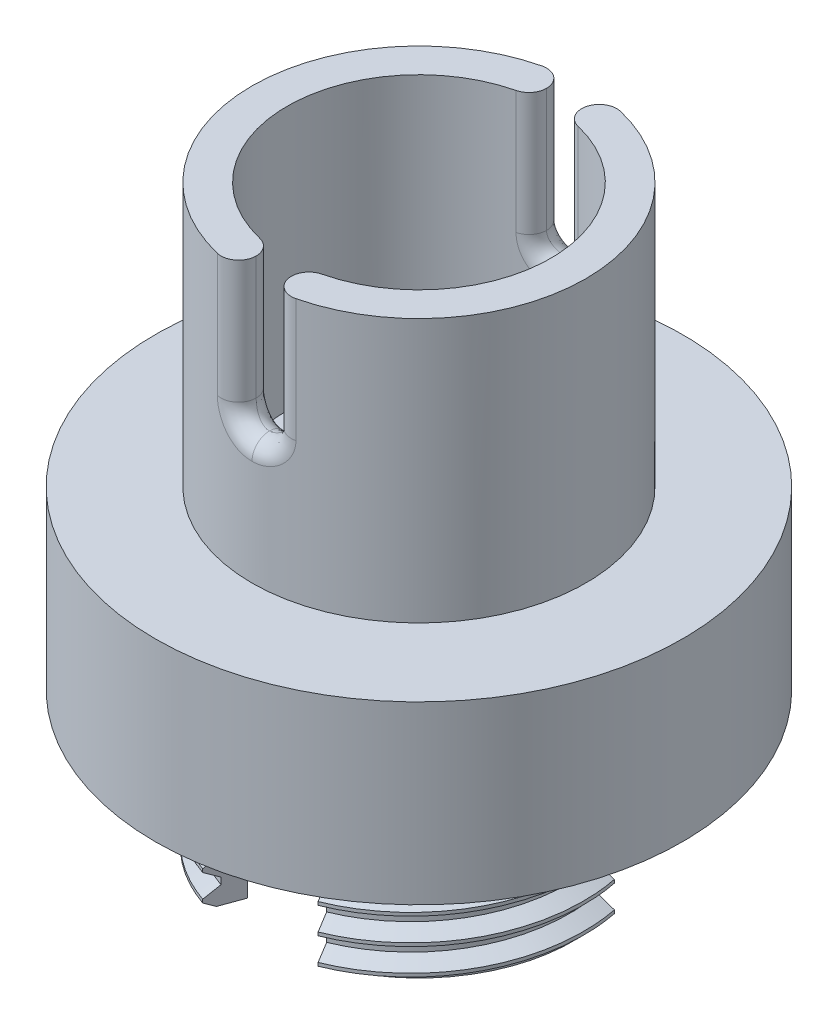
SolidWorks part; units mm, degrees
ref_plane "Front" through (0, 0, 0) normal (0, 0, 1) x (1, 0, 0)
ref_plane "Top" through (0, 0, 0) normal (0, 1, 0) x (1, 0, 0)
ref_plane "Right" through (0, 0, 0) normal (1, 0, 0) x (0, 0, -1)
sketch "Sketch1" plane through (0, 0, 0) normal (0, 1, 0) x (1, 0, 0)
  circle A0 centre (0, 0) radius 15
extrude "Boss-Extrude1" add sketch "Sketch1" along normal blind 10
sketch "Sketch2" plane through (0, 10, 0) normal (0, 1, 0) x (1, 0, 0)
  circle A0 centre (0, 0) radius 7.5
  circle A1 centre (0, 0) radius 9.5
extrude "Boss-Extrude2" add sketch "Sketch2" along normal blind 15
sketch "Sketch3" plane through (0, 0, 0) normal (0, -1, 0) x (1, 0, 0)
  circle A0 centre (0, 0) radius 7.6
  circle A1 centre (0, 0) radius 9.6
extrude "Boss-Extrude3" add sketch "Sketch3" along normal blind 8
sketch "Sketch4" plane through (0, 0, 0) normal (0, 0, 1) x (1, 0, 0)
  line L0 (0, 9.9863) -> (0, -13.3125) construction
  line L1 (0, 7.6) -> (0, -7.6)
  arc A1 (0, 7.6) -> (0, -7.6) centre (0, 0) cw
revolve "Cut-Revolve1" cut sketch "Sketch4" angle 360 about L0
sketch "Sketch5" plane through (0, -8, 0) normal (0, -1, 0) x (1, 0, 0)
  line L0 (0, 16.258) -> (0, 0) construction
  line L1 (-3.2834, 9.021) -> (-2.5994, 7.1417)
  line L2 (3.2834, 9.021) -> (2.5994, 7.1417)
  line L3 (9.4542, -1.667) -> (7.4845, -1.3197)
  line L4 (6.1708, -7.354) -> (4.8852, -5.8219)
  line L5 (-6.1708, -7.354) -> (-4.8852, -5.8219)
  line L6 (-9.4542, -1.667) -> (-7.4845, -1.3197)
  circle A0 centre (0, 0) radius 9.6 construction
  circle A1 centre (0, 0) radius 7.6 construction
  arc A2 (-3.2834, 9.021) -> (3.2834, 9.021) centre (0, 0) cw
  arc A3 (2.5994, 7.1417) -> (-2.5994, 7.1417) centre (0, 0) ccw
  arc A4 (4.8852, -5.8219) -> (7.4845, -1.3197) centre (0, 0) ccw
  arc A5 (9.4542, -1.667) -> (6.1708, -7.354) centre (0, 0) cw
  arc A6 (-7.4845, -1.3197) -> (-4.8852, -5.8219) centre (0, 0) ccw
  arc A7 (-6.1708, -7.354) -> (-9.4542, -1.667) centre (0, 0) cw
  point P23 (0, 0)
  dimension "D1" = 20
  dimension "D2" = 3
extrude "Cut-Extrude1" cut sketch "Sketch5" against normal blind 8
thread "Thread1" pitch 1.5 method cut profile "Thread Profile1" start angle 0, offset 2, length 9, pitch 1.5, diameter 19.2
ref_plane "Plane1" through (9.6, -10, 0) normal (0, 0, 1) x (1, 0, 0)
sketch "Thread Profile1" plane through (9.6, -10, 0) normal (0, 0, 1) x (1, 0, 0)
  line L0 (0, 0) -> (0, 1.5) construction
  line L11 (0, 0) -> (0, 1.3125)
  line L12 (0, 1.3125) -> (-0.8119, 0.8437)
  line L13 (-0.8119, 0.8437) -> (-0.8119, 0.4687)
  line L15 (-0.8119, 0.4687) -> (0, 0)
  line L17 (-0.8119, 0.6562) -> (0, 0.6562) construction
  point P2 (0, 0)
  dimension "Pitch" = 1.5
  dimension "Profile_Angle" = 60
  dimension "Profile_Land" = 0.375
  dimension "Profile_Height" = 0.8119
sketch "Sketch9" plane through (0, 25, 0) normal (0, 1, 0) x (1, 0, 0)
  line L0 (0, 12.6584) -> (0, 0) construction
  line L6 (-1, 11.3386) -> (1, 11.3386)
  line L7 (-1, 11.3386) -> (-1, -11.1386)
  line L8 (-1, -11.1386) -> (1, -11.1386)
  line L9 (1, 11.3386) -> (1, -11.1386)
  point P19 (0, 0)
  dimension "D1" = 1
extrude "Cut-Extrude2" cut sketch "Sketch9" against normal blind 8
fillet "Fillet2" radius 1 4 edges at (-1, 17, -8.4401) (1, 17, -8.4401) (1, 17, 8.4401) (-1, 17, 8.4401)
fillet "Fillet3" radius 1 16 edges at (1, 21.5, -7.433) (-1, 21.5, -7.433) (-0.6215, 17.2166, -7.4742) (-1, 21.5, -9.4472) (-0.7824, 17.3773, -9.4677) (1, 21.5, -9.4472) (-1, 21.5, 7.433) (-0.7834, 17.3785, 7.459) (1, 21.5, 7.433) (1, 21.5, 9.4472) (-1, 21.5, 9.4472) (-0.6227, 17.2176, 9.4796) (0.7834, 17.3785, -7.459) (0.6227, 17.2176, -9.4796) (0.6215, 17.2166, 7.4742) (0.7824, 17.3773, 9.4677)
